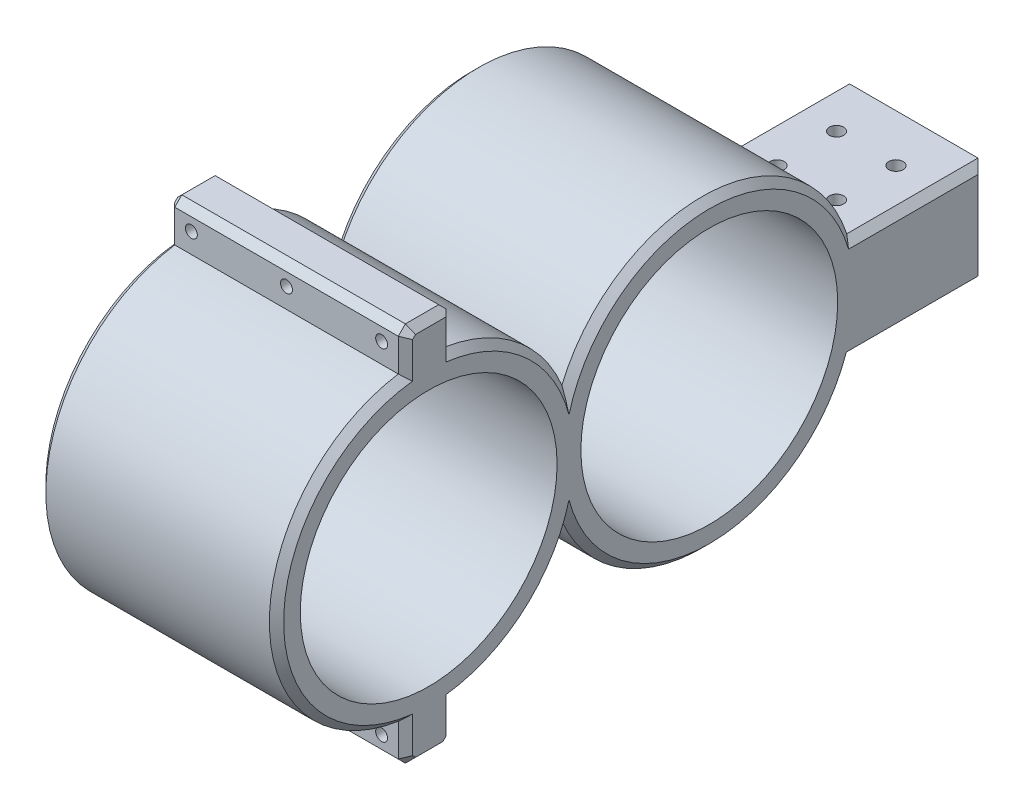
SolidWorks part; units mm, degrees
ref_plane "前视基准面" through (0, 0, 0) normal (0, 0, 1) x (1, 0, 0)
ref_plane "上视基准面" through (0, 0, 0) normal (0, 1, 0) x (1, 0, 0)
ref_plane "右视基准面" through (0, 0, 0) normal (1, 0, 0) x (0, 0, -1)
sketch "草图2" plane through (0, 0, 0) normal (1, 0, 0) x (0, 0, -1)
  circle A0 centre (0, 0) radius 32
  dimension "D1" = 64
extrude "凸台-拉伸1" add sketch "草图2" along normal blind 50
sketch "草图3" plane through (50, 0, 0) normal (1, 0, 0) x (0, 0, -1)
  circle A0 centre (0, 0) radius 27
  dimension "D1" = 54
extrude "切除-拉伸1" cut sketch "草图3" against normal through all
sketch "草图4" plane through (50, 0, 0) normal (1, 0, 0) x (0, 0, -1)
  line L1 (25.0799, 10) -> (117, 10)
  line L2 (25.0799, 10) -> (25.0799, -10)
  line L3 (25.0799, -10) -> (117, -10)
  line L4 (117, 10) -> (117, -10)
  line L5 (25.0799, 10) -> (117, -10) construction
  line L6 (25.0799, -10) -> (117, 10) construction
  circle A0 centre (0, 0) radius 27 construction
  circle A1 centre (0, 0) radius 32 construction
  point P0 (71.0399, 0)
  dimension "D1" = 117
  dimension "D2" = 20
extrude "凸台-拉伸2" add sketch "草图4" against normal blind 30
sketch "草图5" plane through (50, 0, 0) normal (1, 0, 0) x (0, 0, -1)
  circle A0 centre (0, 0) radius 27
  dimension "D1" = 54
extrude "切除-拉伸2" cut sketch "草图5" against normal through all
sketch "草图8" plane through (50, 0, 0) normal (1, 0, 0) x (0, 0, -1)
  line L0 (-32, 0) -> (117, 0) construction
  line L1 (5.0998, 26.5516) -> (-4.9002, 26.5516)
  line L2 (5.0998, 26.5516) -> (5.0998, 40)
  line L3 (5.0998, 40) -> (-4.9002, 40)
  line L4 (-4.9002, 26.5516) -> (-4.9002, 40)
  line L5 (5.0998, 26.5516) -> (-4.9002, 40) construction
  line L6 (5.0998, 40) -> (-4.9002, 26.5516) construction
  line L7 (117, -10) -> (117, 10) construction
  line L8 (5.0998, -40) -> (-4.9002, -40)
  line L9 (-4.9002, -26.5516) -> (-4.9002, -40)
  line L10 (5.0998, -26.5516) -> (-4.9002, -26.5516)
  line L11 (5.0998, -26.5516) -> (5.0998, -40)
  line L12 (0.0998, 50.6797) -> (0.0998, -34.5244) construction
  circle A0 centre (0, 0) radius 27 construction
  arc A1 (30.3974, 10) -> (30.3974, -10) centre (0, 0) ccw construction
  arc A2 (30.3974, 10) -> (30.3974, -10) centre (0, 0) ccw construction
  point P0 (0.0998, 33.2758)
  dimension "D1" = 10
  dimension "D2" = 40
extrude "凸台-拉伸4" add sketch "草图8" against normal up to surface (50 mm away) up to face at (0, 0, -27)
sketch "草图9" plane through (0, 0, 4.9002) normal (0, 0, 1) x (1, 0, 0)
  line L0 (0, 35.8113) -> (50, 35.8113) construction
  line L1 (0, 40) -> (0, 31.6226) construction
  line L2 (50, 40) -> (50, 31.6226) construction
  line L3 (25, 40) -> (25, 31.6226) construction
  line L4 (0, 40) -> (50, 40) construction
  line L5 (50, 31.6226) -> (0, 31.6226) construction
  line L6 (0, 0) -> (28.5789, 0) construction
  circle A0 centre (5, 35.8113) radius 1.25
  circle A1 centre (45, 35.8113) radius 1.25
  circle A2 centre (45, -35.8113) radius 1.25
  circle A3 centre (5, -35.8113) radius 1.25
  circle A4 centre (25, 35.8113) radius 1.25
  circle A5 centre (25, -35.8113) radius 1.25
  dimension "D1" = 2.5
  dimension "D2" = 2.5
  dimension "D4" = 2.5
  dimension "D3" = 5
extrude "切除-拉伸4" cut sketch "草图9" against normal up to next
sketch "草图10" plane through (50, 0, 0) normal (1, 0, 0) x (0, 0, -1)
  circle A0 centre (0, 0) radius 27
  dimension "D1" = 54
extrude "切除-拉伸5" cut sketch "草图10" against normal through all
chamfer "倒角2" distance 1.5 angle 45 4 edges at (25, -40, 4.9002) (25, -40, -5.0998) (25, 40, -5.0998) (25, 40, 4.9002)
chamfer "倒角3" distance 1.5 angle 45 24 edges at (0, -35.0455, -5.0998) (0, -39.25, -4.3498) (0, -40, -0.0998) (0, -39.25, 4.1502) (0, -35.0613, 4.9002) (0, 0, -32) (0, 35.0455, -5.0998) (0, 39.25, -4.3498) (0, 40, -0.0998) (0, 39.25, 4.1502) (0, 35.0613, 4.9002) (0, 0, 32) (50, 35.0455, -5.0998) (50, 24.3402, -20.7739) (50, -24.3402, -20.7739) (50, -35.0455, -5.0998) (50, -39.25, -4.3498) (50, -40, -0.0998) (50, -39.25, 4.1502) (50, -35.0613, 4.9002) (50, 40, -0.0998) (50, 39.25, 4.1502) (50, 35.0613, 4.9002) (50, 0, 32)
sketch "草图13" plane through (50, 0, 0) normal (1, 0, 0) x (0, 0, -1)
  line L0 (117, 0) -> (27, 0) construction
  line L1 (117, -10) -> (117, 10) construction
  circle A0 centre (59, 0) radius 32
  circle A1 centre (0, 0) radius 27 construction
  point P9 (0, 0)
  point P10 (0, 0)
  dimension "D1" = 64
  dimension "D2" = 59
extrude "凸台-拉伸5" add sketch "草图13" against normal blind 50
sketch "草图14" plane through (50, 0, 0) normal (1, 0, 0) x (0, 0, -1)
  circle A0 centre (59, 0) radius 27
  arc A1 (89.3974, 10) -> (28.7055, 10.3075) centre (59, 0) ccw construction
  dimension "D1" = 54
extrude "切除-拉伸8" cut sketch "草图14" against normal through all
sketch "草图17" plane through (0, 10, 0) normal (0, 1, 0) x (1, 0, 0)
  line L0 (35, 89.3974) -> (35, 117) construction
  line L1 (50, 89.3974) -> (20, 89.3974) construction
  line L2 (20, 117) -> (50, 117) construction
  circle A0 centre (41.25, 94.5) radius 1.5
  circle A1 centre (28.75, 94.5) radius 1.5
  circle A2 centre (28.75, 107) radius 1.5
  circle A3 centre (41.25, 107) radius 1.5
  point P14 (0, 0)
  point P15 (0, 0)
  dimension "D1" = 3
  dimension "D2" = 12.5
  dimension "D3" = 12.5
  dimension "D4" = 12.5
  dimension "D5" = 10
extrude "切除-拉伸11" cut sketch "草图17" against normal through all
chamfer "倒角4" distance 1.5 angle 45 7 edges at (0, 0, -91) (20, 10, -103.1987) (50, -31.9996, -59.1621) (50, 10, -103.1987) (50, 31.9996, -59.1621) (20, 0, -117) (50, 0, -117)
sketch "草图11" plane through (0, 0, 0) normal (0, 0, 1) x (1, 0, 0)
  line L1 (60.6516, -49.0819) -> (-27.9407, -49.0819)
  line L2 (60.6516, -49.0819) -> (60.6516, 47.2432)
  line L3 (60.6516, 47.2432) -> (-27.9407, 47.2432)
  line L4 (-27.9407, -49.0819) -> (-27.9407, 47.2432)
  line L5 (60.6516, -49.0819) -> (-27.9407, 47.2432) construction
  line L6 (60.6516, 47.2432) -> (-27.9407, -49.0819) construction
  point P0 (16.3554, -0.9194)
extrude "切除-拉伸9" [suppressed] cut sketch "草图11" along normal through all
sketch "草图16" [suppressed] plane through (0, 0, 0) normal (0, 0, 1) x (1, 0, 0)
  circle A0 centre (45, 35.8113) radius 1.5
  circle A1 centre (5, 35.8113) radius 1.5
  circle A2 centre (5, -35.8113) radius 1.5
  circle A3 centre (45, -35.8113) radius 1.5
  circle A4 centre (25, 35.8113) radius 1.5
  circle A5 centre (25, 35.8113) radius 1.25 construction
  circle A6 centre (25, -35.8113) radius 1.5
  dimension "D1" = 3
  dimension "D2" = 3
  dimension "D3" = 3
extrude "切除-拉伸10" [suppressed] cut sketch "草图16" against normal up to next
